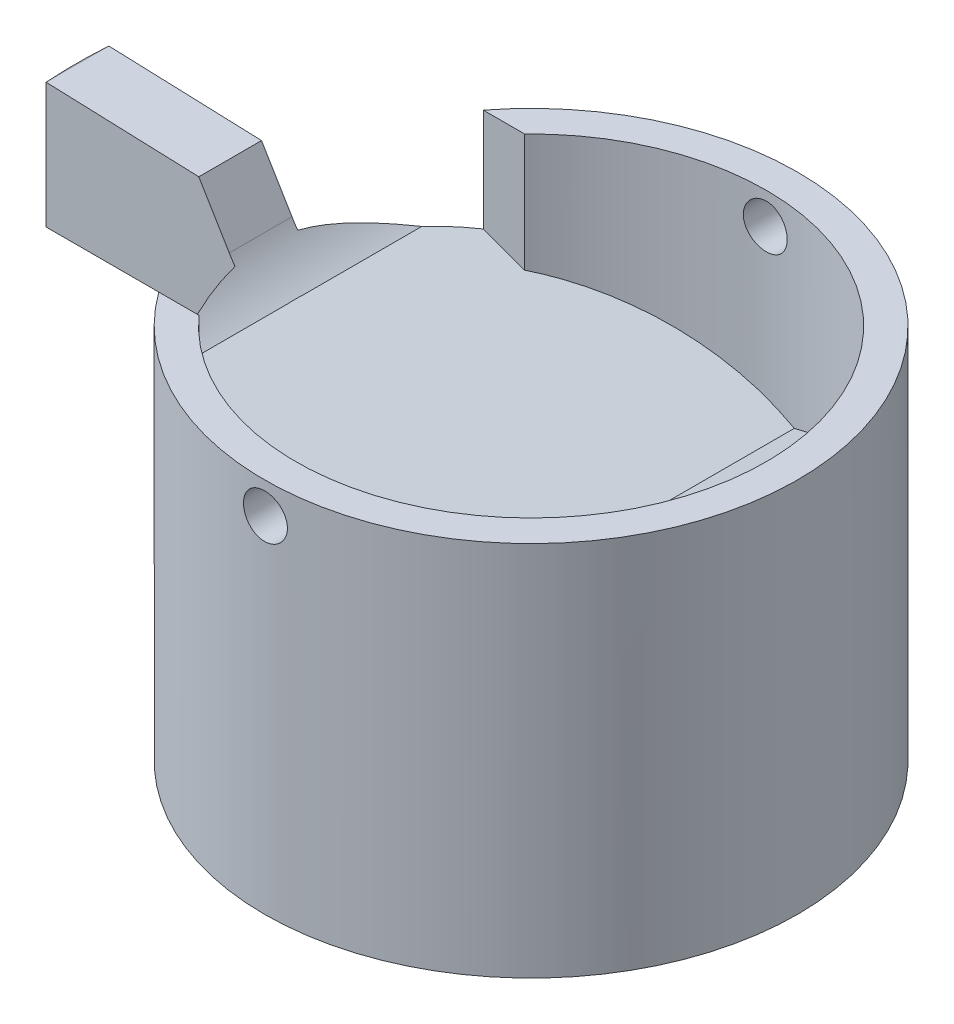
SolidWorks part; units mm, degrees
ref_plane "Front Plane" through (0, 0, 0) normal (0, 0, 1) x (1, 0, 0)
ref_plane "Top Plane" through (0, 0, 0) normal (0, 1, 0) x (1, 0, 0)
ref_plane "Right Plane" through (0, 0, 0) normal (1, 0, 0) x (0, 0, -1)
sketch "Sketch1" plane through (0, 0, 0) normal (0, 1, 0) x (1, 0, 0)
  circle A0 centre (0, 0) radius 9.525
  circle A1 centre (0, 0) radius 10.795
  dimension "D1" = 19.05
  dimension "D2" = 1.27
extrude "Boss-Extrude1" add sketch "Sketch1" along normal blind 2.54 contours A1
sketch "Sketch2" plane through (0, 2.54, 0) normal (0, 1, 0) x (1, 0, 0)
  circle A0 centre (0, 0) radius 9.525
  circle A1 centre (0, 0) radius 10.795
  circle A2 centre (0, 0) radius 10.795 construction
  dimension "D1" = 19.05
extrude "Boss-Extrude2" add sketch "Sketch2" along normal blind 12.7
ref_plane "Plane1" through (0, 12.7, 0) normal (0, 1, 0) x (1, 0, 0)
sketch "Sketch3" plane through (0, 0, 0) normal (0, 0, 1) x (1, 0, 0)
  line L1 (9.525, 2.54) -> (-9.525, 2.54) construction
  line L2 (-9.525, 11.43) -> (-9.525, 2.54)
  line L3 (-9.525, 2.54) -> (9.525, 2.54)
  line L4 (-9.525, 11.43) -> (9.525, 4.5134)
  line L5 (9.525, 4.5134) -> (9.525, 2.54)
  dimension "D1" = 8.89
  dimension "D2" = 1.9734
extrude "Boss-Extrude3" add sketch "Sketch3" along normal mid plane 19.05 contours L2 L3 L5 L4
sketch "Sketch4" plane through (0, 15.24, 0) normal (0, 1, 0) x (1, 0, 0)
  circle A0 centre (0, 0) radius 10.795
  circle A1 centre (0, 0) radius 13.4704
  circle A2 centre (0, 0) radius 10.795 construction
extrude "Cut-Extrude1" cut sketch "Sketch4" against normal up to surface (15.24 mm away) up to face at (0, 0, 10.795)
sketch "Sketch5" plane through (0, 15.24, 0) normal (0, 1, 0) x (1, 0, 0)
  line L0 (0, 0) -> (-16.3634, 0) construction
  line L2 (-9.525, 1.27) -> (-18.3712, 1.27)
  line L3 (-9.525, 1.27) -> (-9.525, -1.27)
  line L4 (-9.525, -1.27) -> (-18.3712, -1.27)
  arc A0 (-18.3712, 1.27) -> (-18.3712, -1.27) centre (0, 0) ccw
  circle A1 centre (0, 0) radius 10.795 construction
  dimension "D1" = 7.62
  dimension "D2" = 1.27
  dimension "D3" = 1.27
  dimension "D4" = 9.525
extrude "Boss-Extrude4" add sketch "Sketch5" against normal blind 5.08
sketch "Sketch7" plane through (0, 0, -1.27) normal (0, 0, -1) x (-1, 0, 0)
  line L0 (18.3712, 13.6281) -> (18.3712, 15.24)
  line L2 (18.3712, 15.24) -> (8.9498, 14.8981)
  line L6 (10.72, 15.24) -> (18.3712, 15.24) construction
  line L7 (18.3712, 10.16) -> (18.3712, 15.24) construction
  line L9 (18.3712, 15.24) -> (8.9801, 16.51)
  line L14 (8.9801, 16.51) -> (8.9498, 14.8981)
  dimension "D1" = 1.6119
  dimension "D2" = 0
  dimension "D3" = 0
  dimension "D4" = 1.6119
extrude "Cut-Extrude6" cut sketch "Sketch7" against normal blind 3.81 and the other way blind 1.27 contours L2 L14 L9
fillet "Fillet1" radius 2.54 2 edges at (-9.836, 15.24, -2.54) (-9.836, 15.24, 2.54)
ref_plane "Plane2" through (0, 0, 0) normal (0, 0, -1) x (-1, 0, 0)
ref_plane "Plane3" through (0, 0, -6.604) normal (0, 0, -1) x (-1, 0, 0)
sketch "Sketch8" plane through (0, 0, 0) normal (0, 0, 1) x (1, 0, 0)
  line L0 (-10.606, 14.9582) -> (10.795, 14.9582) construction
  line L1 (-10.4919, 14.9541) -> (-10.72, 14.9623) construction
  line L2 (10.795, 0) -> (10.795, 15.24) construction
  line L3 (0, -15.24) -> (0, 15.24) construction
  line L4 (10.795, 15.24) -> (-10.1269, 15.24) construction
  line L5 (9.525, 15.24) -> (-8.7213, 15.24) construction
  circle A0 centre (0, 13.97) radius 0.889
  point P12 (0, 0)
  dimension "D2" = 1.778
  dimension "D1" = 1.27
extrude "Cut-Extrude7" cut sketch "Sketch8" against normal through all both and the other way through all
sketch "Sketch9" plane through (0, 0, -6.604) normal (0, 0, -1) x (-1, 0, 0)
  line L1 (9.525, 11.43) -> (-9.525, 4.5134) construction
  line L2 (18.3712, 15.24) -> (10.72, 14.9623) construction
  line L3 (11.6344, 14.9955) -> (5.6712, 16.0646)
  line L4 (9.5183, 11.4276) -> (7.1376, 10.5632)
  line L5 (7.1376, 10.5632) -> (5.6712, 10.0308)
  line L6 (5.6712, 16.0646) -> (5.6712, 10.0308)
  line L7 (18.3712, 10.16) -> (18.3712, 15.24) construction
  line L8 (10.72, 10.16) -> (10.72, 14.9623) construction
  line L10 (10.9542, 12.9596) -> (12.1869, 15.0156)
  line L11 (12.1869, 15.0156) -> (5.6712, 16.0646)
  arc A0 (11.6344, 14.9955) -> (9.5183, 11.4276) centre (6.6917, 15.5155) cw
  dimension "D1" = 12.7
  dimension "D2" = 0.9144
  dimension "D3" = 0.0254
extrude "Cut-Extrude8" cut sketch "Sketch9" against normal blind 12.954 contours L3 A0 L10 L11 | L3 L6 L5 L4 A0 region at (-8.6541, 15.5372, -6.604)
sketch "Sketch10" plane through (0, 0, 0) normal (0, 0, 1) x (1, 0, 0)
  line L0 (-7.0995, 10.5494) -> (9.5248, 10.5494)
  line L3 (9.5248, 10.5494) -> (-7.0995, 4.5143)
  line L4 (9.5248, 10.5494) -> (9.5248, 4.5135)
  line L5 (9.525, 4.5134) -> (-7.0995, 10.5494) construction
  line L6 (9.5248, 4.5135) -> (-7.0995, 4.5143)
  point P3 (0, 0)
  dimension "D1" = 16.6243
  dimension "D2" = 6.035
extrude "Boss-Extrude5" add sketch "Sketch10" along normal mid plane 21.336 contours L6 L4 L3 region at (3.9834, 6.5257, 0)
sketch "Sketch11" plane through (0, 15.24, 0) normal (0, 1, 0) x (1, 0, 0)
  line L0 (-9.9486, -10.9806) -> (-10.4527, -2.6969)
  line L1 (-10.4527, 2.6969) -> (-10.0687, 10.8706)
  line L2 (-10.4527, -2.6969) -> (-10.4527, 2.6969)
  arc A0 (-10.4527, -2.6969) -> (-10.4527, 2.6969) centre (0, 0) ccw
  arc A1 (-9.9486, -10.9806) -> (-10.0687, 10.8706) centre (0, 0) ccw
  arc M9 (-8.7298, -6.35) -> (-8.5393, 6.604) centre (0, 0) ccw
extrude "Cut-Extrude9" cut sketch "Sketch11" against normal up to surface (15.24 mm away) contours L0 A1 L1 A0 M9 region at (-9.8119, 15.24, 6.8151) up to face at (0, 0, 10.795)
equation "\"D1@Sketch9\"=\"D1@Sketch5\" + .2"
